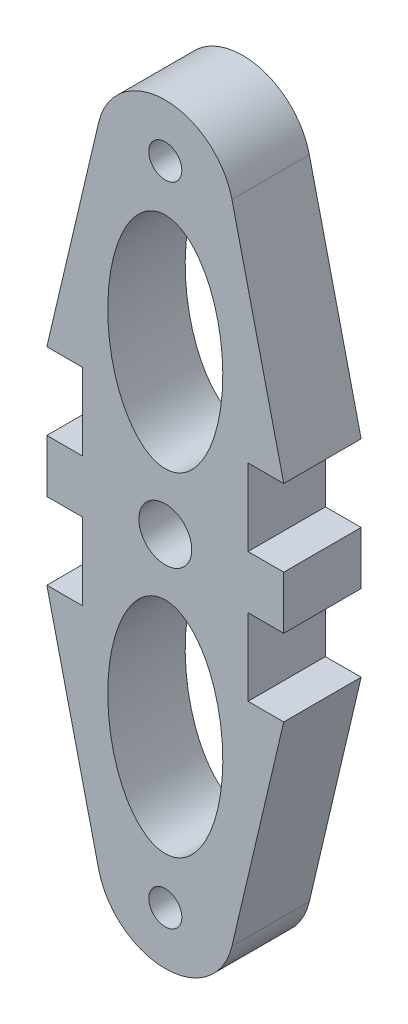
SolidWorks part; units mm, degrees
material "Acrylic (Medium-high impact)"
ref_plane "Front Plane" through (0, 0, 0) normal (0, 0, 1) x (1, 0, 0)
ref_plane "Top Plane" through (0, 0, 0) normal (0, 1, 0) x (1, 0, 0)
ref_plane "Right Plane" through (0, 0, 0) normal (1, 0, 0) x (0, 0, -1)
sketch "Sketch1" plane through (0, 0, 0) normal (0, 0, 1) x (1, 0, 0)
  line L0 (-213.0435, 465.4024) -> (49786.9565, 465.4024) construction
  line L1 (781.4092, 465.4024) -> (778.7092, 465.4024)
  line L2 (781.4092, 465.4024) -> (781.4092, 471.2024)
  line L3 (781.4092, 471.2024) -> (778.7092, 471.2024)
  line L4 (787.6592, -515.9255) -> (787.6592, 49484.0745) construction
  line L5 (-215.2235, 463.4024) -> (49784.7765, 463.4024) construction
  line L6 (793.9092, 471.2024) -> (793.9092, 487.8374) construction
  line L7 (-217.5077, 461.4024) -> (49782.4923, 461.4024) construction
  line L8 (785.6592, -537.0976) -> (785.6592, 49462.9024) construction
  line L9 (789.6592, -536.5976) -> (789.6592, 49463.4024) construction
  line L10 (793.9092, 465.4024) -> (796.6092, 465.4024)
  line L11 (781.4092, 471.2024) -> (793.9092, 471.2024) construction
  line L12 (793.9092, 471.2024) -> (796.6092, 471.2024)
  line L13 (793.9092, 465.4024) -> (793.9092, 471.2024)
  line L14 (778.7092, 465.4024) -> (778.7092, 461.4024)
  line L15 (796.6092, 465.4024) -> (796.6092, 461.4024)
  line L16 (786.4092, 487.8374) -> (782.6227, 487.8374) construction
  line L17 (781.4092, 461.4024) -> (778.7092, 461.4024)
  line L19 (781.4092, 455.6024) -> (778.7092, 455.6024)
  line L20 (781.4092, 461.4024) -> (781.4092, 455.6024)
  line L21 (793.9092, 461.4024) -> (796.6092, 461.4024)
  line L22 (793.9092, 461.4024) -> (793.9092, 455.6024)
  line L23 (793.9092, 455.6024) -> (796.6092, 455.6024)
  line L24 (778.7092, 471.2024) -> (782.6227, 487.8374)
  line L25 (792.6956, 487.8374) -> (796.6092, 471.2024)
  line L26 (792.6956, 438.9674) -> (796.6092, 455.6024)
  line L27 (788.9092, 438.9674) -> (792.6956, 438.9674) construction
  line L28 (786.4092, 438.9674) -> (782.6227, 438.9674) construction
  line L29 (778.7092, 455.6024) -> (782.6227, 438.9674)
  line L35 (788.9092, 487.8374) -> (792.6956, 487.8374) construction
  arc A0 (782.6227, 487.8374) -> (792.6956, 487.8374) centre (787.6592, 486.6525) cw
  arc A1 (782.6227, 438.9674) -> (792.6956, 438.9674) centre (787.6592, 440.1522) ccw
  circle A3 centre (787.6592, 487.8374) radius 1.25
  circle A5 centre (787.6592, 438.9674) radius 1.25
  circle A6 centre (787.6592, 463.4024) radius 2
  ellipse E0 centre (787.6592, 475.9981) end of major axis (787.6592, 484.3002) minor radius 4.3465
  ellipse E1 centre (787.6592, 450.8066) end of major axis (787.6592, 442.5045) minor radius 4.3465
  point P10 (778.7092, 463.4024)
  point P19 (796.6092, 463.4024)
  dimension "D1" = 4
  dimension "D3" = 5.8
  dimension "D10" = 5.174
  dimension "D2" = 2.7
  dimension "D4" = 24.435
  dimension "D5" = 12.5
  dimension "D6" = 16.6042
  dimension "D7" = 8.693
  dimension "D8" = 2.2937
extrude "Boss-Extrude1" add sketch "Sketch1" along normal blind 5.85 contours L3 A3 A5 region at (782.0052, 468.3024, 0)
